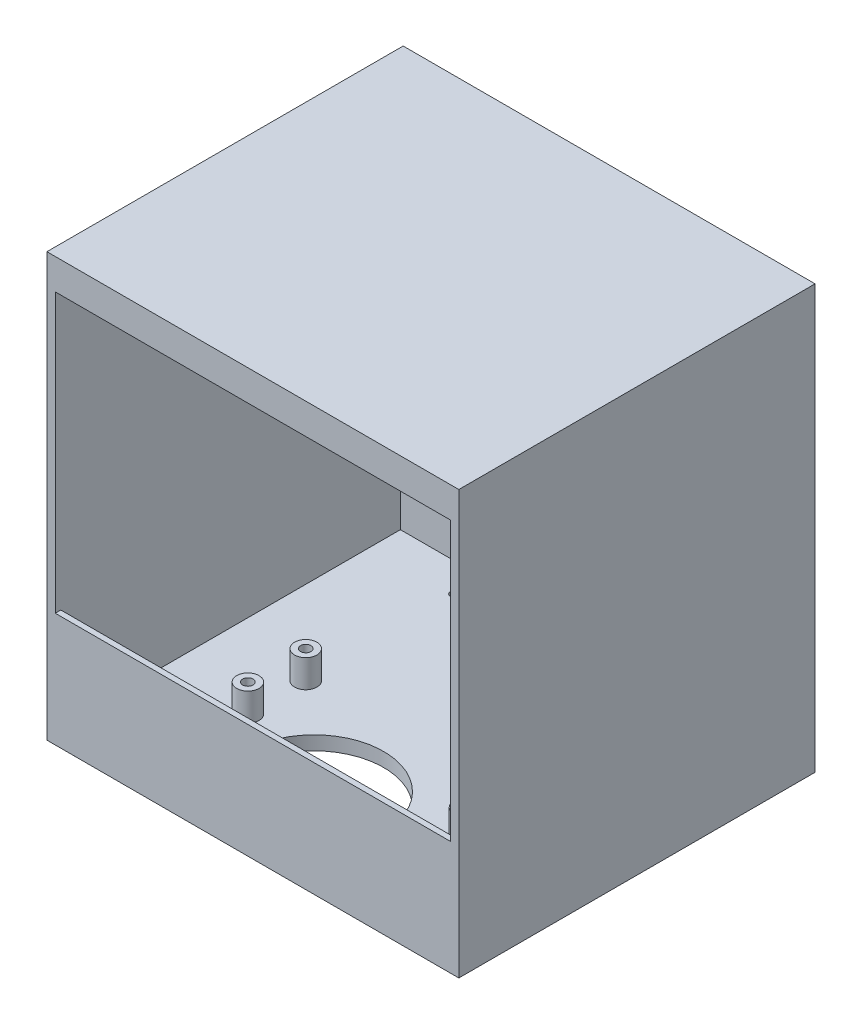
SolidWorks part; units mm, degrees
ref_plane "Front Plane" through (0, 0, 0) normal (0, 0, 1) x (1, 0, 0)
ref_plane "Top Plane" through (0, 0, 0) normal (0, 1, 0) x (1, 0, 0)
ref_plane "Right Plane" through (0, 0, 0) normal (1, 0, 0) x (0, 0, -1)
sketch "Sketch1" plane through (0, 0, 0) normal (0, 0, 1) x (1, 0, 0)
  line L1 (0, 0) -> (469.9, 0)
  line L2 (0, 0) -> (0, -482.6)
  line L3 (0, -482.6) -> (469.9, -482.6)
  line L4 (469.9, 0) -> (469.9, -482.6)
  dimension "D1" = 469.9
  dimension "D2" = 482.6
extrude "full box" add sketch "Sketch1" against normal blind 406.4
sketch "Sketch2" plane through (0, 0, 0) normal (0, 0, 1) x (1, 0, 0)
  line L0 (0, 0) -> (0, -482.6) construction
  line L1 (9.525, -34.925) -> (460.375, -34.925)
  line L2 (9.525, -34.925) -> (9.525, -352.425)
  line L3 (9.525, -352.425) -> (460.375, -352.425)
  line L4 (460.375, -34.925) -> (460.375, -352.425)
  line L5 (0, -482.6) -> (469.9, -482.6) construction
  dimension "D1" = 450.85
  dimension "D2" = 9.525
  dimension "D3" = 317.5
  dimension "D4" = 130.175
extrude "inside cut" cut sketch "Sketch2" against normal blind 393.7
sketch "Sketch3" plane through (0, -352.425, 0) normal (0, 1, 0) x (1, 0, 0)
  line L0 (460.375, 393.7) -> (460.375, 0) construction
  line L1 (9.525, 393.7) -> (460.375, 393.7)
  line L2 (9.525, 393.7) -> (9.525, 6.35)
  line L3 (9.525, 6.35) -> (460.375, 6.35)
  line L4 (460.375, 393.7) -> (460.375, 6.35)
  line L5 (9.525, 0) -> (460.375, 0) construction
  dimension "D1" = 0
  dimension "D2" = 6.35
extrude "floor cut" cut sketch "Sketch3" against normal blind 114.3
sketch "Sketch4" plane through (0, -466.725, 0) normal (0, 1, 0) x (1, 0, 0)
  line L2 (9.525, 6.35) -> (460.375, 6.35) construction
  line L3 (460.375, 6.35) -> (460.375, 393.7) construction
  circle A0 centre (219.075, 85.725) radius 79.375
  point P6 (0, 0)
  point P7 (250.825, 125.8154)
  point P8 (239.079, 47.3144)
  point P9 (250.825, 46.4404)
  point P10 (250.825, 125.8154)
  dimension "D1" = 158.75
  dimension "D3" = 79.375
  dimension "D2" = 241.3
extrude "drain hole" cut sketch "Sketch4" against normal through all
sketch "Sketch5" plane through (0, -466.725, 0) normal (0, 1, 0) x (1, 0, 0)
  line L0 (460.375, 6.35) -> (460.375, 393.7) construction
  line L1 (460.375, 393.7) -> (9.525, 393.7) construction
  circle A0 centre (104.775, 124.46) radius 12.7
  circle A1 centre (352.425, 124.46) radius 12.7
  circle A2 centre (352.425, 190.5) radius 12.7
  circle A3 centre (104.775, 190.5) radius 12.7
  point P8 (352.425, 361.95)
  point P9 (104.775, 361.95)
  point P14 (0, 0)
  point P15 (104.775, 124.46)
  point P16 (352.425, 124.46)
  point P17 (352.425, 190.5)
  point P19 (104.775, 190.5)
  dimension "D1" = 25.4
  dimension "D5" = 171.45
  dimension "D2" = 107.95
  dimension "D3" = 247.65
  dimension "D4" = 31.75
  dimension "D6" = 66.04
extrude "pegs" add sketch "Sketch5" along normal blind 31.75 separate body
sketch "positions of holes in pegs" plane through (0, -434.975, 0) normal (0, 1, 0) x (1, 0, 0)
  point P0 (104.775, 190.5)
  point P1 (104.775, 124.46)
  point P3 (352.425, 124.46)
  point P5 (352.425, 190.5)
hole_wizard "holes in pegs" positions "Sketch18" profile "Sketch19" tap size "1/4-18 NPSM" standard "ANSI Inch"
sketch "Sketch18" plane through (0, -434.975, 0) normal (0, 1, 0) x (1, 0, 0)
  point P0 (104.775, 124.46)
  point P3 (104.775, 190.5)
  point P6 (352.425, 190.5)
  point P9 (352.425, 124.46)
sketch "Sketch19" plane through (104.775, -434.975, -124.46) normal (1, 0, 0) x (0, 0, 1)
  line L0 (0, 0) -> (0, 35.3213)
  line L1 (0, 35.3213) -> (5.9436, 31.75)
  line L2 (5.9436, 31.75) -> (5.9436, 0)
  line L5 (5.9436, 0) -> (0, 0)
  line L10 (0, 35.3213) -> (-5.9436, 31.75) construction
  line L11 (0, -6.35) -> (0, 107.95) construction
  dimension "Tap Drill Dia." = 11.8872
  dimension "Tap Drill Depth" = 31.75
  dimension "Drill Angle" = 118
cosmetic thread "Hole Thread9" parameters "D1"=26.7208, "D2"=13.3604
cosmetic thread "Hole Thread10" parameters "D1"=26.7208, "D2"=13.3604
cosmetic thread "Hole Thread11" parameters "D1"=26.7208, "D2"=13.3604
cosmetic thread "Hole Thread12" parameters "D1"=26.7208, "D2"=13.3604
sketch "holes in floor" plane through (0, -466.725, 0) normal (0, 1, 0) x (1, 0, 0)
  line L0 (460.375, 6.35) -> (460.375, 393.7) construction
  point P0 (104.775, 361.95)
  point P1 (352.425, 361.95)
  point P5 (0, 0)
  dimension "D1" = 171.45
  dimension "D2" = 247.65
  dimension "D3" = 107.95
hole_wizard "1/4-18 NPSM Tapped Hole3" positions "Sketch23" profile "Sketch24" tap size "1/4-18 NPSM" standard "ANSI Inch"
sketch "Sketch23" plane through (0, -466.725, 0) normal (0, 1, 0) x (1, 0, 0)
  point P0 (104.775, 361.95)
  point P3 (352.425, 361.95)
sketch "Sketch24" plane through (104.775, -466.725, -361.95) normal (1, 0, 0) x (0, 0, 1)
  line L0 (0, 0) -> (0, 35.3213)
  line L1 (0, 35.3213) -> (5.9436, 31.75)
  line L2 (5.9436, 31.75) -> (5.9436, 0)
  line L5 (5.9436, 0) -> (0, 0)
  line L10 (0, 35.3213) -> (-5.9436, 31.75) construction
  line L11 (0, -6.35) -> (0, 107.95) construction
  dimension "Tap Drill Dia." = 11.8872
  dimension "Tap Drill Depth" = 31.75
  dimension "Drill Angle" = 118
cosmetic thread "Hole Thread13" parameters "D1"=15.875, "D2"=13.3604
cosmetic thread "Hole Thread14" parameters "D1"=15.875, "D2"=13.3604
